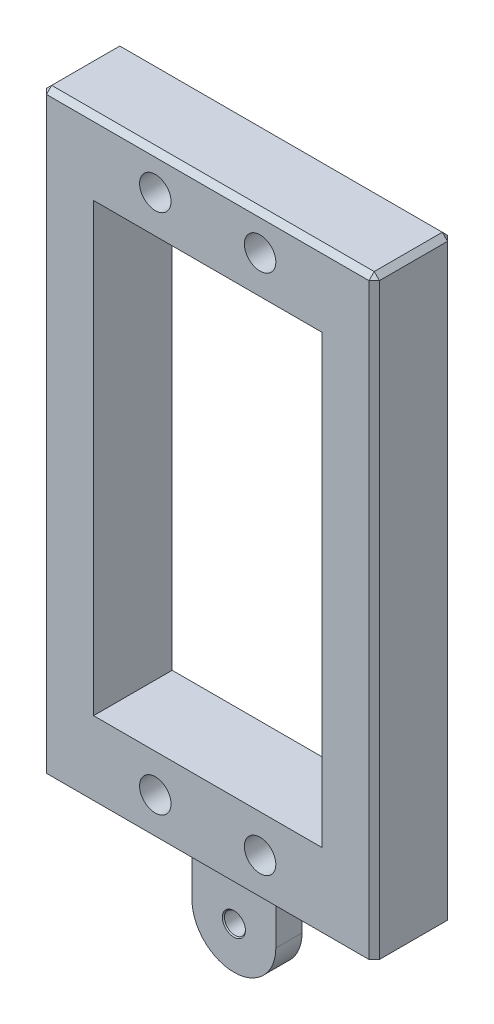
SolidWorks part; units mm, degrees
ref_plane "Front Plane" through (0, 0, 0) normal (0, 0, 1) x (1, 0, 0)
ref_plane "Top Plane" through (0, 0, 0) normal (0, 1, 0) x (1, 0, 0)
ref_plane "Right Plane" through (0, 0, 0) normal (1, 0, 0) x (0, 0, -1)
sketch "Sketch2" plane through (0, 0, 0) normal (0, 0, 1) x (1, 0, 0)
  line L0 (-8.9, -20.2879) -> (8.9, -20.2879) construction
  line L1 (10.8879, -21.2879) -> (-10.8879, -21.2879)
  line L2 (10.8879, -21.2879) -> (10.8879, 21.2879)
  line L3 (10.8879, 21.2879) -> (-10.8879, 21.2879)
  line L4 (-10.8879, -21.2879) -> (-10.8879, 21.2879)
  line L5 (8.9, 20.2879) -> (-8.9, 20.2879) construction
  line L6 (-9.8879, 19.3) -> (-9.8879, -19.3) construction
  line L7 (9.8879, -19.3) -> (9.8879, 19.3) construction
  line L8 (3.75, -27.3) -> (-3.75, -27.3) construction
  line L9 (15.8879, 28.3) -> (-15.8879, 28.3)
  line L10 (15.8879, 28.3) -> (15.8879, -28.3)
  line L11 (15.8879, -28.3) -> (-15.8879, -28.3)
  line L12 (-15.8879, 28.3) -> (-15.8879, -28.3)
  line L13 (15.8879, 28.3) -> (-15.8879, -28.3) construction
  line L14 (15.8879, -28.3) -> (-15.8879, 28.3) construction
  circle A0 centre (5, -24.8896) radius 1.5
  circle A1 centre (-5, -24.8896) radius 1.5
  circle A2 centre (5, 24.8896) radius 1.5
  circle A3 centre (-5, 24.8896) radius 1.5
  arc A4 (-3.75, -26.7) -> (-6.25, -26.7) centre (-5, -24.8896) ccw construction
  point P26 (0, 0)
  dimension "D1" = 3
  dimension "D2" = 1
  dimension "D3" = 1
  dimension "D4" = 1
  dimension "D5" = 1
  dimension "D6" = 1
  dimension "D7" = 5
extrude "Boss-Extrude1" add sketch "Sketch2" along normal blind 7.5
ref_plane "MidSlide" through (0, 0, 3.75) normal (0, 0, 1) x (1, 0, 0)
sketch "Sketch3" plane through (0, -28.3, 0) normal (0, -1, 0) x (1, 0, 0)
  line L1 (-4, 5) -> (4, 5)
  line L2 (-4, 5) -> (-4, 2.5)
  line L3 (-4, 2.5) -> (4, 2.5)
  line L4 (4, 5) -> (4, 2.5)
  line L5 (17.4767, 3.75) -> (-17.4767, 3.75) construction
  point P6 (-4, 3.75)
  point P8 (0, 5)
  dimension "D2" = 8
  dimension "D3" = 2.5
extrude "Boss-Extrude2" add sketch "Sketch3" along normal blind 10
sketch "Sketch4" plane through (0, 0, 5) normal (0, 0, 1) x (1, 0, 0)
  line L0 (4, -38.3) -> (-4, -38.3) construction
  circle A0 centre (0, -34.3) radius 1
  point P4 (0, -38.3)
  dimension "D1" = 2
  dimension "D2" = 4
extrude "Cut-Extrude1" cut sketch "Sketch4" against normal through all
fillet "Fillet1" radius 4 2 edges at (4, -38.3, 3.75) (-4, -38.3, 3.75)
fillet "Fillet3" radius 0.5 4 edges at (4, -28.3, 3.75) (0, -28.3, 2.5) (-4, -28.3, 3.75) (0, -28.3, 5)
chamfer "Chamfer1" distance 0.1 angle 45 2 edges at (1, -34.3, 2.5) (1, -34.3, 5)
chamfer "Chamfer2" distance 0.5 angle 45 8 edges at (-15.8879, 0, 0) (15.8879, 0, 0) (15.8879, 28.3, 3.75) (0, 28.3, 0) (-15.8879, 28.3, 3.75) (15.8879, 0, 7.5) (0, 28.3, 7.5) (-15.8879, 0, 7.5)
